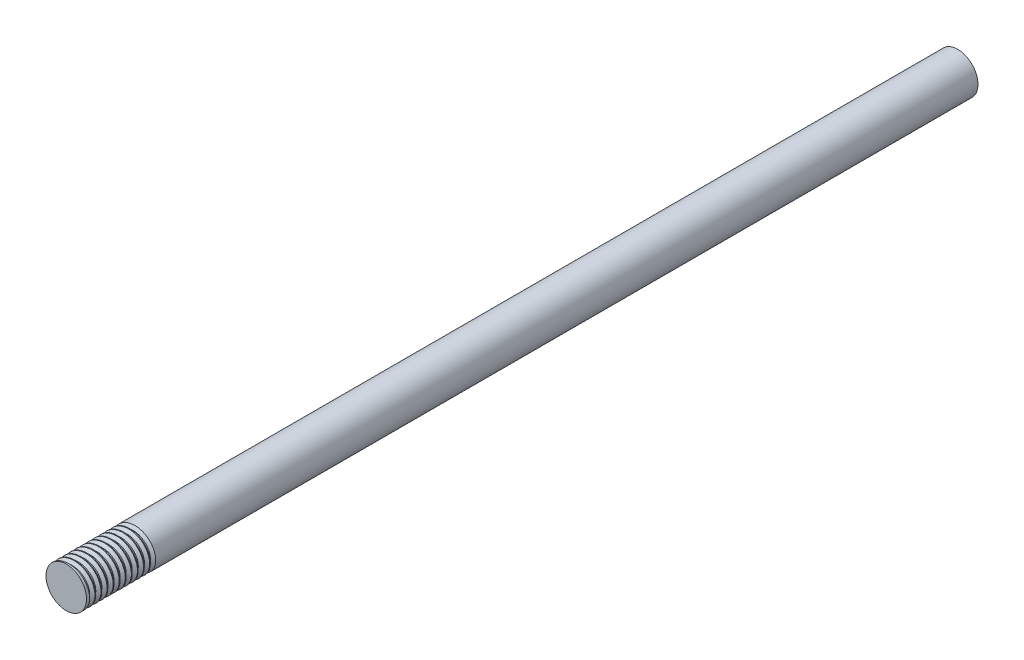
SolidWorks part; units mm, degrees
ref_plane "Alzado" through (0, 0, 0) normal (0, 0, 1) x (1, 0, 0)
ref_plane "Planta" through (0, 0, 0) normal (0, 1, 0) x (1, 0, 0)
ref_plane "Vista lateral" through (0, 0, 0) normal (1, 0, 0) x (0, 0, -1)
sketch "Croquis1" plane through (0, 0, 0) normal (0, 0, 1) x (1, 0, 0)
  circle A0 centre (0, 0) radius 1.5
  dimension "D1" = 3
extrude "Saliente-Extruir1" add sketch "Croquis1" along normal blind 66
cosmetic thread "Rosca cosmética1" parameters "D2"=2.439
thread "Rosca1" pitch 0.45 method cut profile "Perfil de rosca1" start angle 0, offset 0, length 5, pitch 0.45, diameter 3
ref_plane "Plano1" through (-1.5, 0, 66) normal (0, -1, 0) x (-1, 0, 0)
sketch "Perfil de rosca1" plane through (-1.5, 0, 66) normal (0, -1, 0) x (-1, 0, 0)
  line L0 (0, 0) -> (0, 0.45) construction
  line L11 (0, 0) -> (0, 0.3937)
  line L12 (0, 0.3937) -> (-0.2436, 0.2531)
  line L13 (-0.2436, 0.2531) -> (-0.2436, 0.1406)
  line L15 (-0.2436, 0.1406) -> (0, 0)
  line L17 (-0.2436, 0.1969) -> (0, 0.1969) construction
  point P2 (0, 0)
  dimension "Pitch" = 0.45
  dimension "Profile_Angle" = 60
  dimension "Profile_Land" = 0.1125
  dimension "Profile_Height" = 0.2436
equation "\"D1@Saliente-Extruir1\"=66"
